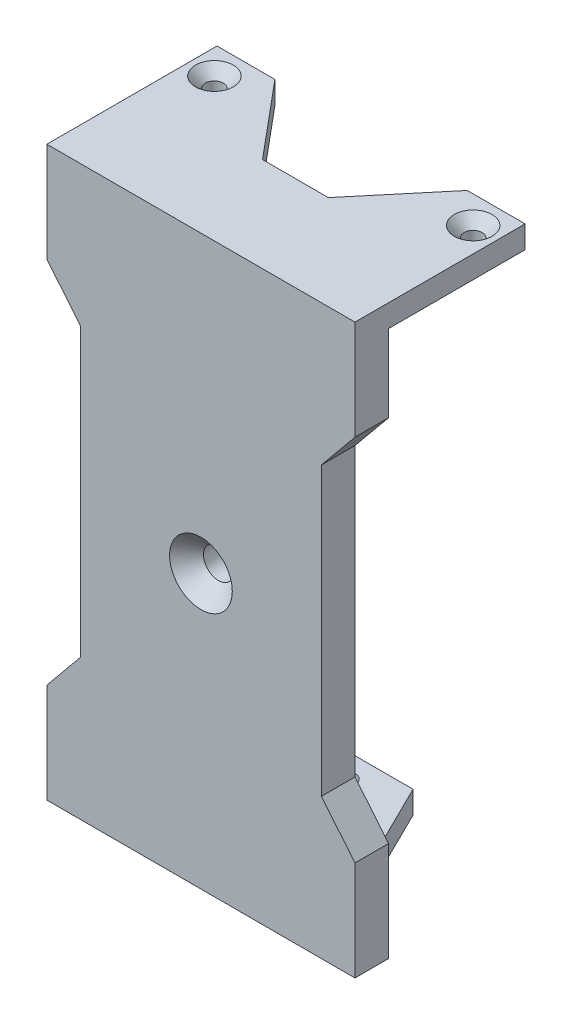
SolidWorks part; units mm, degrees
ref_plane "Front Plane" through (0, 0, 0) normal (0, 0, 1) x (1, 0, 0)
ref_plane "Top Plane" through (0, 0, 0) normal (0, 1, 0) x (1, 0, 0)
ref_plane "Right Plane" through (0, 0, 0) normal (1, 0, 0) x (0, 0, -1)
sketch "Sketch1" plane through (0, 0, 0) normal (0, 0, 1) x (1, 0, 0)
  line L0 (0, 0) -> (55, 0) construction
  line L1 (55, 0) -> (55, -93.4) construction
  line L2 (55, -93.4) -> (0, -93.4) construction
  line L3 (0, -93.4) -> (0, 0) construction
  line L7 (55, 0) -> (0, 0)
  line L8 (55, -46.7) -> (0, -46.7) construction
  line L10 (27.5, 0) -> (27.5, -102.43) construction
  line L11 (55, 0) -> (55, -13.7874)
  line L12 (55, -13.7874) -> (49, -21.0837)
  line L13 (49, -21.0837) -> (49, -72.3163)
  line L14 (55, -79.6126) -> (49, -72.3163)
  line L15 (55, -93.4) -> (55, -79.6126)
  line L16 (55, -93.4) -> (0, -93.4)
  line L17 (0, -93.4) -> (0, -79.6126)
  line L18 (0, -79.6126) -> (6, -72.3163)
  line L19 (6, -21.0837) -> (6, -72.3163)
  line L20 (0, -13.7874) -> (6, -21.0837)
  line L21 (0, 0) -> (0, -13.7874)
  circle A1 centre (48, -6) radius 4.5 construction
  point P14 (49, -46.7)
  point P16 (27.5, -93.4)
  point P24 (27.5, -93.4)
  dimension "D4" = 9
  dimension "D1" = 55
  dimension "D2" = 93.4
  dimension "D3" = 6
  dimension "D5" = 7
  dimension "D6" = 6
extrude "Boss-Extrude1" add sketch "Sketch1" along normal blind 6 contours L19 L18 L17 L16 L15 L14 L13 L12 L11 L7 L21 L20
sketch "Sketch2" plane through (0, 0, 0) normal (0, 1, 0) x (1, 0, 0)
  line L0 (0, -6) -> (0, 0)
  line L1 (0, 0) -> (0, 24.3682)
  line L2 (27.5, -6) -> (27.5, 12.073) construction
  line L3 (55, -6) -> (0, -6) construction
  line L4 (0, 24.3682) -> (10.336, 24.3682)
  line L5 (10.336, 24.3682) -> (21.6251, 10.8693)
  line L6 (21.6251, 10.8693) -> (33.3749, 10.8693)
  line L7 (55, 0) -> (55, 24.3682)
  line L8 (55, 24.3682) -> (44.664, 24.3682)
  line L9 (44.664, 24.3682) -> (33.3749, 10.8693)
  line L10 (0, -6) -> (55, -6)
  line L11 (55, -6) -> (55, 0)
  point P16 (27.5, 10.8693)
extrude "Boss-Extrude2" add sketch "Sketch2" along normal blind 4
sketch "Sketch3" plane through (0, -93.4, 0) normal (0, -1, 0) x (1, 0, 0)
  line L0 (55, 6) -> (0, 6)
  line L1 (0, 6) -> (0, 0)
  line L2 (0, 0) -> (7.9746, 0)
  line L3 (55, 0) -> (0, 0) construction
  line L4 (7.9746, 0) -> (20, -24.3649)
  line L5 (27.5, 6) -> (27.5, -18.9998) construction
  line L6 (20, -24.3649) -> (35, -24.3649)
  line L7 (55, 6) -> (55, 0)
  line L8 (55, 0) -> (47.0254, 0)
  line L9 (47.0254, 0) -> (35, -24.3649)
  line L10 (55, 0) -> (0, 0) construction
  point P16 (27.5, -24.3649)
  dimension "D1" = 15
extrude "Boss-Extrude3" add sketch "Sketch3" along normal blind 4
sketch "Sketch4" plane through (0, 0, 6) normal (0, 0, 1) x (1, 0, 0)
  line L0 (0, 4) -> (55, 4) construction
  line L1 (0, 4) -> (0, -13.7874) construction
  circle A0 centre (27.5, -48.6) radius 2.7
  dimension "D1" = 5.4
  dimension "D2" = 52.6
  dimension "D3" = 27.5
extrude "Cut-Extrude1" cut sketch "Sketch4" against normal up to surface (6 mm away) up to face at (27.5, -59.375, 0)
ref_plane "Plane1" through (0, 0, 2.85) normal (0, 0, 1) x (1, 0, 0)
sketch "Sketch5" plane through (0, 0, 2.85) normal (0, 0, 1) x (1, 0, 0)
  circle A0 centre (27.5, -48.6) radius 2.7 construction
  circle A1 centre (27.5, -48.6) radius 2.7
sketch "Sketch6" plane through (0, 0, 6) normal (0, 0, 1) x (1, 0, 0)
  circle A0 centre (27.5, -48.6) radius 5.6
  dimension "D1" = 11.2
loft "Cut-Loft1" cut profiles "Sketch6", "Sketch5" connector at (23.0345, -45.2208, 6) connector at (25.1786, -47.2212, 2.85)
sketch "Sketch7" plane through (0, 4, 0) normal (0, 1, 0) x (1, 0, 0)
  line L0 (27.5, -6) -> (27.5, 28.4444) construction
  line L1 (0, -6) -> (55, -6) construction
  line L3 (55, -6) -> (55, 24.3682) construction
  circle A0 centre (50.6, 19.5) radius 1.6
  circle A1 centre (4.4, 19.5) radius 1.6
  dimension "D1" = 3.2
  dimension "D2" = 4.4
  dimension "D3" = 25.5
extrude "Cut-Extrude2" cut sketch "Sketch7" against normal up to surface (4 mm away) up to face at (27.5, 0, -14.9015)
sketch "Sketch8" plane through (0, -97.4, 0) normal (0, -1, 0) x (1, 0, 0)
  line L0 (55, 6) -> (0, 6) construction
  circle A0 centre (27.5, -20) radius 1.6
  point P5 (27.5, 6)
  dimension "D1" = 3.2
  dimension "D2" = 26
extrude "Cut-Extrude3" cut sketch "Sketch8" against normal up to surface (4 mm away) up to face at (27.5, -93.4, -12.1825)
ref_plane "Plane2" through (0, -95.5, 0) normal (0, -1, 0) x (-1, 0, 0)
sketch "Sketch9" plane through (0, -95.5, 0) normal (0, -1, 0) x (-1, 0, 0)
  circle A0 centre (-27.5, 20) radius 1.6 construction
  circle A1 centre (-27.5, 20) radius 1.6
sketch "Sketch10" plane through (0, -97.4, 0) normal (0, -1, 0) x (1, 0, 0)
  circle A0 centre (27.5, -20) radius 3.375
  dimension "D1" = 6.75
loft "Cut-Loft2" cut profiles "Sketch10", "Sketch9" connector at (28.1449, -97.4, -16.6872) connector at (26.6572, -95.5, -21.36)
ref_plane "Plane3" through (0, 2.1, 0) normal (0, 1, 0) x (1, 0, 0)
sketch "Sketch11" plane through (0, 2.1, 0) normal (0, 1, 0) x (1, 0, 0)
  circle A0 centre (50.6, 19.5) radius 1.6 construction
  circle A1 centre (50.6, 19.5) radius 1.6
sketch "Sketch12" plane through (0, 4, 0) normal (0, 1, 0) x (1, 0, 0)
  circle A0 centre (50.6, 19.5) radius 3.375
  dimension "D2" = 6.75
loft "Cut-Loft3" cut profiles "Sketch12", "Sketch11" connector at (50.3139, 4, -22.8629) connector at (50.1018, 2.1, -21.0204)
pattern_linear "LPattern1" count 2 spacing 46.2 along (-1, 0, 0) of "Cut-Loft3"
